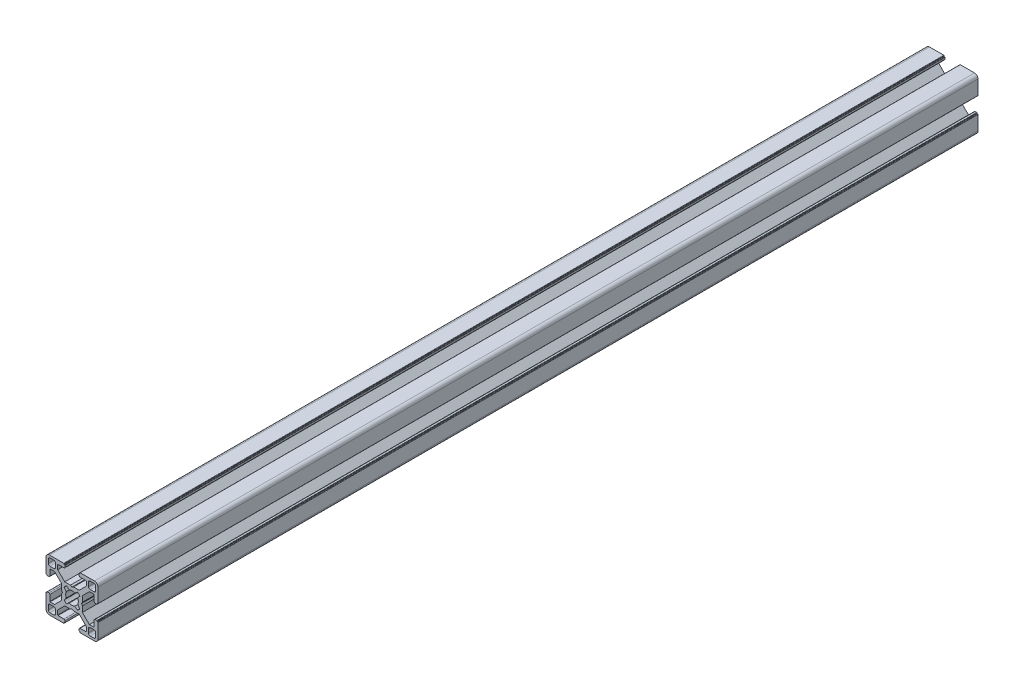
SolidWorks part; units mm, degrees
material "6061 Alloy"
ref_plane "Front" through (0, 0, 0) normal (0, 0, 1) x (1, 0, 0)
ref_plane "Top" through (0, 0, 0) normal (0, 1, 0) x (1, 0, 0)
ref_plane "Right" through (0, 0, 0) normal (1, 0, 0) x (0, 0, -1)
sketch "Sketch1" plane through (0, 0, 0) normal (0, 0, 1) x (1, 0, 0)
  line L0 (13.7, 12.7) -> (13.7, 10.5)
  line L1 (10.5, 9.5) -> (12.7, 9.5)
  line L2 (9.5, 12.7) -> (9.5, 10.5)
  line L3 (10.5, 13.7) -> (12.7, 13.7)
  line L4 (3.1359, 4.5184) -> (1.6001, 3.2806)
  line L5 (3.2806, 1.6001) -> (4.5053, 3.1547)
  line L6 (6.0045, 0.9) -> (5.4849, 0)
  line L7 (6.0045, 4.2045) -> (6.0045, 0.9)
  line L8 (0, -5.4849) -> (0.9, -6)
  line L9 (0.9, -6) -> (4.2045, -6)
  line L10 (4.2045, -6) -> (8.25, -10.05)
  line L11 (8.25, -10.05) -> (8.25, -12.6)
  line L12 (4.65, -12.8) -> (8.05, -12.8)
  line L13 (4.05, -14.3) -> (4.05, -13.4)
  line L14 (4.25, -14.5) -> (4.35, -14.5)
  line L15 (4.55, -14.8) -> (4.55, -14.7)
  line L16 (4.75, -15) -> (13, -15)
  line L17 (15, -13) -> (15, -4.75)
  line L18 (14.7, -4.55) -> (14.8, -4.55)
  line L19 (14.5, -4.35) -> (14.5, -4.25)
  line L20 (13.4, -4.05) -> (14.3, -4.05)
  line L21 (12.8, -8.05) -> (12.8, -4.65)
  line L22 (12.6, -8.25) -> (10.05, -8.25)
  line L23 (10.05, -8.25) -> (6.0045, -4.2045)
  line L24 (6.0045, -4.2045) -> (6.0045, -0.9)
  line L25 (6.0045, -0.9) -> (5.4849, 0)
  line L26 (10.05, 8.25) -> (6.0045, 4.2045)
  line L27 (12.6, 8.25) -> (10.05, 8.25)
  line L28 (12.8, 8.05) -> (12.8, 4.65)
  line L29 (13.4, 4.05) -> (14.3, 4.05)
  line L30 (14.5, 4.35) -> (14.5, 4.25)
  line L31 (14.7, 4.55) -> (14.8, 4.55)
  line L32 (15, 13) -> (15, 4.75)
  line L33 (4.75, 15) -> (13, 15)
  line L34 (4.55, 14.8) -> (4.55, 14.7)
  line L35 (4.25, 14.5) -> (4.35, 14.5)
  line L36 (4.05, 14.3) -> (4.05, 13.4)
  line L37 (4.65, 12.8) -> (8.05, 12.8)
  line L38 (8.25, 10.05) -> (8.25, 12.6)
  line L39 (4.2045, 6) -> (8.25, 10.05)
  line L40 (0.9, 6) -> (4.2045, 6)
  line L41 (0, 5.4849) -> (0.9, 6)
  line L42 (-13.7, -12.7) -> (-13.7, -10.5)
  line L43 (-10.5, -9.5) -> (-12.7, -9.5)
  line L44 (-9.5, -12.7) -> (-9.5, -10.5)
  line L45 (-10.5, -13.7) -> (-12.7, -13.7)
  line L46 (-3.1359, -4.5184) -> (-1.6001, -3.2806)
  line L47 (-3.2806, -1.6001) -> (-4.5053, -3.1547)
  line L48 (0, 5.4849) -> (-0.9, 6)
  line L49 (-0.9, 6) -> (-4.2045, 6)
  line L50 (-4.2045, 6) -> (-8.25, 10.05)
  line L51 (-8.25, 10.05) -> (-8.25, 12.6)
  line L52 (-4.65, 12.8) -> (-8.05, 12.8)
  line L53 (-4.05, 14.3) -> (-4.05, 13.4)
  line L54 (-4.25, 14.5) -> (-4.35, 14.5)
  line L55 (-4.55, 14.8) -> (-4.55, 14.7)
  line L56 (-4.75, 15) -> (-13, 15)
  line L57 (-15, 13) -> (-15, 4.75)
  line L58 (-14.7, 4.55) -> (-14.8, 4.55)
  line L59 (-14.5, 4.35) -> (-14.5, 4.25)
  line L60 (-13.4, 4.05) -> (-14.3, 4.05)
  line L61 (-12.8, 8.05) -> (-12.8, 4.65)
  line L62 (-12.6, 8.25) -> (-10.05, 8.25)
  line L63 (-10.05, 8.25) -> (-6.0045, 4.2045)
  line L64 (-6.0045, -0.9) -> (-5.4849, 0)
  line L65 (-6.0045, -4.2045) -> (-6.0045, -0.9)
  line L66 (-10.05, -8.25) -> (-6.0045, -4.2045)
  line L67 (-12.6, -8.25) -> (-10.05, -8.25)
  line L68 (-12.8, -8.05) -> (-12.8, -4.65)
  line L69 (-13.4, -4.05) -> (-14.3, -4.05)
  line L70 (-14.5, -4.35) -> (-14.5, -4.25)
  line L71 (-14.7, -4.55) -> (-14.8, -4.55)
  line L72 (-15, -13) -> (-15, -4.75)
  line L73 (-4.75, -15) -> (-13, -15)
  line L74 (-4.55, -14.8) -> (-4.55, -14.7)
  line L75 (-4.25, -14.5) -> (-4.35, -14.5)
  line L76 (-4.05, -14.3) -> (-4.05, -13.4)
  line L77 (3.2806, -1.6001) -> (4.5053, -3.1547)
  line L78 (3.1359, -4.5184) -> (1.6001, -3.2806)
  line L79 (-4.65, -12.8) -> (-8.05, -12.8)
  line L80 (-8.25, -10.05) -> (-8.25, -12.6)
  line L81 (-4.2045, -6) -> (-8.25, -10.05)
  line L82 (-0.9, -6) -> (-4.2045, -6)
  line L83 (0, -5.4849) -> (-0.9, -6)
  line L84 (10.5, -13.7) -> (12.7, -13.7)
  line L85 (9.5, -12.7) -> (9.5, -10.5)
  line L86 (10.5, -9.5) -> (12.7, -9.5)
  line L87 (13.7, -12.7) -> (13.7, -10.5)
  line L88 (-6.0045, 4.2045) -> (-6.0045, 0.9)
  line L89 (-6.0045, 0.9) -> (-5.4849, 0)
  line L90 (-3.2806, 1.6001) -> (-4.5053, 3.1547)
  line L91 (-3.1359, 4.5184) -> (-1.6001, 3.2806)
  line L92 (-10.5, 13.7) -> (-12.7, 13.7)
  line L93 (-9.5, 12.7) -> (-9.5, 10.5)
  line L94 (-10.5, 9.5) -> (-12.7, 9.5)
  line L95 (-13.7, 12.7) -> (-13.7, 10.5)
  line L96 (-23.4857, 0) -> (20.9308, 0) construction
  line L97 (0, 17.9563) -> (0, -17.361) construction
  arc A0 (13.7, 12.7) -> (12.7, 13.7) centre (12.7, 12.7) ccw
  arc A1 (12.7, 9.5) -> (13.7, 10.5) centre (12.7, 10.5) ccw
  arc A2 (9.5, 10.5) -> (10.5, 9.5) centre (10.5, 10.5) ccw
  arc A3 (10.5, 13.7) -> (9.5, 12.7) centre (10.5, 12.7) ccw
  arc A4 (1.6001, 3.2806) -> (-1.6001, 3.2806) centre (0, 0) ccw
  arc A5 (8.25, -12.6) -> (8.05, -12.8) centre (8.05, -12.6) cw
  arc A6 (4.65, -12.8) -> (4.05, -13.4) centre (4.65, -13.4) ccw
  arc A7 (4.05, -14.3) -> (4.25, -14.5) centre (4.25, -14.3) ccw
  arc A8 (4.35, -14.5) -> (4.55, -14.7) centre (4.35, -14.7) cw
  arc A9 (4.55, -14.8) -> (4.75, -15) centre (4.75, -14.8) ccw
  arc A10 (13, -15) -> (15, -13) centre (13, -13) ccw
  arc A11 (15, -4.75) -> (14.8, -4.55) centre (14.8, -4.75) ccw
  arc A12 (14.7, -4.55) -> (14.5, -4.35) centre (14.7, -4.35) cw
  arc A13 (14.5, -4.25) -> (14.3, -4.05) centre (14.3, -4.25) ccw
  arc A14 (13.4, -4.05) -> (12.8, -4.65) centre (13.4, -4.65) ccw
  arc A15 (12.8, -8.05) -> (12.6, -8.25) centre (12.6, -8.05) cw
  arc A16 (4.5053, 3.1547) -> (3.1359, 4.5184) centre (0, 0) ccw
  arc A17 (12.8, 8.05) -> (12.6, 8.25) centre (12.6, 8.05) ccw
  arc A18 (13.4, 4.05) -> (12.8, 4.65) centre (13.4, 4.65) cw
  arc A19 (14.5, 4.25) -> (14.3, 4.05) centre (14.3, 4.25) cw
  arc A20 (14.7, 4.55) -> (14.5, 4.35) centre (14.7, 4.35) ccw
  arc A21 (15, 4.75) -> (14.8, 4.55) centre (14.8, 4.75) cw
  arc A22 (13, 15) -> (15, 13) centre (13, 13) cw
  arc A23 (4.55, 14.8) -> (4.75, 15) centre (4.75, 14.8) cw
  arc A24 (4.35, 14.5) -> (4.55, 14.7) centre (4.35, 14.7) ccw
  arc A25 (4.05, 14.3) -> (4.25, 14.5) centre (4.25, 14.3) cw
  arc A26 (4.65, 12.8) -> (4.05, 13.4) centre (4.65, 13.4) cw
  arc A27 (8.25, 12.6) -> (8.05, 12.8) centre (8.05, 12.6) ccw
  arc A28 (-13.7, -12.7) -> (-12.7, -13.7) centre (-12.7, -12.7) ccw
  arc A29 (-12.7, -9.5) -> (-13.7, -10.5) centre (-12.7, -10.5) ccw
  arc A30 (-9.5, -10.5) -> (-10.5, -9.5) centre (-10.5, -10.5) ccw
  arc A31 (-10.5, -13.7) -> (-9.5, -12.7) centre (-10.5, -12.7) ccw
  arc A32 (-4.5053, -3.1547) -> (-3.1359, -4.5184) centre (0, 0) ccw
  arc A33 (-3.2806, 1.6001) -> (-3.2806, -1.6001) centre (0, 0) ccw
  arc A34 (-8.25, 12.6) -> (-8.05, 12.8) centre (-8.05, 12.6) cw
  arc A35 (-4.65, 12.8) -> (-4.05, 13.4) centre (-4.65, 13.4) ccw
  arc A36 (-4.05, 14.3) -> (-4.25, 14.5) centre (-4.25, 14.3) ccw
  arc A37 (-4.35, 14.5) -> (-4.55, 14.7) centre (-4.35, 14.7) cw
  arc A38 (-4.55, 14.8) -> (-4.75, 15) centre (-4.75, 14.8) ccw
  arc A39 (-13, 15) -> (-15, 13) centre (-13, 13) ccw
  arc A40 (-15, 4.75) -> (-14.8, 4.55) centre (-14.8, 4.75) ccw
  arc A41 (-14.7, 4.55) -> (-14.5, 4.35) centre (-14.7, 4.35) cw
  arc A42 (-14.5, 4.25) -> (-14.3, 4.05) centre (-14.3, 4.25) ccw
  arc A43 (-13.4, 4.05) -> (-12.8, 4.65) centre (-13.4, 4.65) ccw
  arc A44 (-12.8, 8.05) -> (-12.6, 8.25) centre (-12.6, 8.05) cw
  arc A45 (-4.5053, 3.1547) -> (-3.1359, 4.5184) centre (0, 0) cw
  arc A46 (-12.8, -8.05) -> (-12.6, -8.25) centre (-12.6, -8.05) ccw
  arc A47 (-13.4, -4.05) -> (-12.8, -4.65) centre (-13.4, -4.65) cw
  arc A48 (-14.5, -4.25) -> (-14.3, -4.05) centre (-14.3, -4.25) cw
  arc A49 (3.2806, 1.6001) -> (3.2806, -1.6001) centre (0, 0) cw
  arc A50 (4.5053, -3.1547) -> (3.1359, -4.5184) centre (0, 0) cw
  arc A51 (1.6001, -3.2806) -> (-1.6001, -3.2806) centre (0, 0) cw
  arc A52 (-14.7, -4.55) -> (-14.5, -4.35) centre (-14.7, -4.35) ccw
  arc A53 (-15, -4.75) -> (-14.8, -4.55) centre (-14.8, -4.75) cw
  arc A54 (-13, -15) -> (-15, -13) centre (-13, -13) cw
  arc A55 (-4.55, -14.8) -> (-4.75, -15) centre (-4.75, -14.8) cw
  arc A56 (10.5, -13.7) -> (9.5, -12.7) centre (10.5, -12.7) cw
  arc A57 (9.5, -10.5) -> (10.5, -9.5) centre (10.5, -10.5) cw
  arc A58 (12.7, -9.5) -> (13.7, -10.5) centre (12.7, -10.5) cw
  arc A59 (13.7, -12.7) -> (12.7, -13.7) centre (12.7, -12.7) cw
  arc A60 (-4.35, -14.5) -> (-4.55, -14.7) centre (-4.35, -14.7) ccw
  arc A61 (-4.05, -14.3) -> (-4.25, -14.5) centre (-4.25, -14.3) cw
  arc A62 (-4.65, -12.8) -> (-4.05, -13.4) centre (-4.65, -13.4) cw
  arc A63 (-8.25, -12.6) -> (-8.05, -12.8) centre (-8.05, -12.6) ccw
  arc A64 (-10.5, 13.7) -> (-9.5, 12.7) centre (-10.5, 12.7) cw
  arc A65 (-9.5, 10.5) -> (-10.5, 9.5) centre (-10.5, 10.5) cw
  arc A66 (-12.7, 9.5) -> (-13.7, 10.5) centre (-12.7, 10.5) cw
  arc A67 (-13.7, 12.7) -> (-12.7, 13.7) centre (-12.7, 12.7) cw
  point P81 (15, 15)
  point P82 (0, 15)
  point P203 (0, -15)
  point P204 (15, -15)
  point P206 (0, 0)
  point P207 (15, 0)
  point P219 (-15, 0)
  point P220 (-15, -15)
  point P221 (-15, 15)
  dimension "D6" = 7.3
  dimension "D7" = 11
  dimension "D1" = 30
  dimension "D2" = 15
  dimension "D3" = 30
  dimension "D4" = 8.1
  dimension "D5" = 9
  dimension "D8" = 8.1
extrude "Boss-Extrude1" add sketch "Sketch1" along normal blind 508
